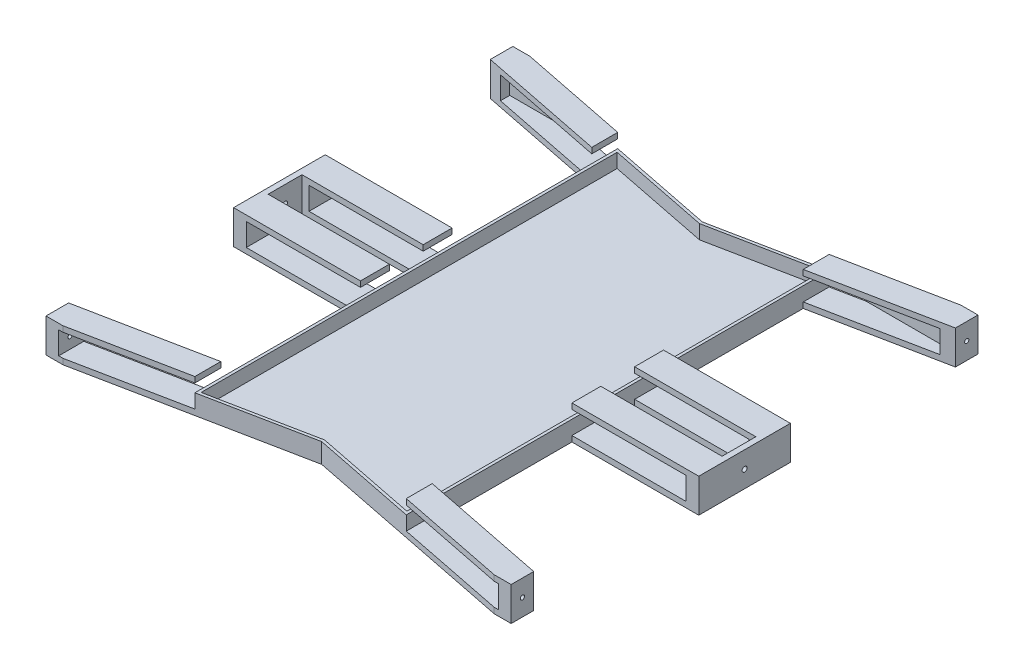
SolidWorks part; units mm, degrees
ref_plane "Front Plane" through (0, 0, 0) normal (0, 0, 1) x (1, 0, 0)
ref_plane "Top Plane" through (0, 0, 0) normal (0, 1, 0) x (1, 0, 0)
ref_plane "Right Plane" through (0, 0, 0) normal (1, 0, 0) x (0, 0, -1)
sketch "Sketch1" plane through (0, 0, 0) normal (0, 1, 0) x (1, 0, 0)
  line L1 (-55, 0) -> (55, 0) construction
  line L2 (165, 32.5) -> (165, -32.5)
  line L3 (165, -32.5) -> (75, -32.5)
  line L4 (75, -32.5) -> (75, -131.6)
  line L5 (75, -131.6) -> (165, -149.6)
  line L6 (165, -149.6) -> (165, -165.6)
  line L7 (165, -165.6) -> (153, -165.6)
  line L8 (153, -165.6) -> (0, -135)
  line L9 (0, -55) -> (0, 55) construction
  line L11 (-165, 32.5) -> (-165, -32.5)
  line L12 (-165, -32.5) -> (-75, -32.5)
  line L13 (-75, -32.5) -> (-75, -131.6)
  line L14 (-75, -131.6) -> (-165, -149.6)
  line L15 (-165, -149.6) -> (-165, -165.6)
  line L16 (-165, -165.6) -> (-153, -165.6)
  line L17 (-153, -165.6) -> (0, -135)
  line L18 (165, 32.5) -> (75, 32.5)
  line L19 (75, 32.5) -> (75, 131.6)
  line L20 (165, 165.6) -> (153, 165.6)
  line L21 (165, 149.6) -> (165, 165.6)
  line L22 (75, 131.6) -> (165, 149.6)
  line L23 (153, 165.6) -> (0, 135)
  line L24 (-165, 149.6) -> (-165, 165.6)
  line L25 (-165, 165.6) -> (-153, 165.6)
  line L26 (-153, 165.6) -> (0, 135)
  line L27 (-75, 131.6) -> (-165, 149.6)
  line L28 (-165, 32.5) -> (-75, 32.5)
  line L29 (-75, 32.5) -> (-75, 131.6)
  line L30 (75, -131.6) -> (75, -150) construction
  line L32 (-75, -131.6) -> (-75, -150) construction
  line L34 (-75, 131.6) -> (-75, 150) construction
  line L36 (75, 131.6) -> (75, 150) construction
  point P21 (165, 0)
  point P33 (-165, 0)
  dimension "D1" = 300
  dimension "D2" = 270
  dimension "D3" = 150
  dimension "D4" = 16
  dimension "D5" = 12
  dimension "D6" = 65
  dimension "D7" = 90
extrude "Boss-Extrude1" add sketch "Sketch1" along normal blind 12 and the other way blind 12
sketch "Sketch2" plane through (0, 0, 165.6) normal (0, 0, 1) x (1, 0, 0)
  line L1 (-156, -8) -> (156, -8)
  line L2 (-156, -8) -> (-156, 8)
  line L3 (-156, 8) -> (156, 8)
  line L4 (156, -8) -> (156, 8)
  line L7 (55, 0) -> (-55, 0) construction
  dimension "D1" = 8
  dimension "D2" = 8
  dimension "D3" = 156
  dimension "D4" = 156
extrude "Cut-Extrude1" cut sketch "Sketch2" against normal blind 320
sketch "Sketch4" plane through (0, 12, 0) normal (0, 1, 0) x (1, 0, 0)
  line L0 (-55, 0) -> (55, 0) construction
  line L1 (-161, 12) -> (-75, 12)
  line L2 (-161, 12) -> (-161, -12)
  line L3 (-161, -12) -> (-75, -12)
  line L4 (-75, 12) -> (-75, -12)
  line L5 (-165, 32.5) -> (-165, -32.5) construction
  line L6 (-75, -32.5) -> (-75, -131.6) construction
  line L7 (0, -55) -> (0, 55) construction
  line L8 (161, -12) -> (75, -12)
  line L9 (75, 12) -> (75, -12)
  line L10 (161, 12) -> (75, 12)
  line L11 (161, 12) -> (161, -12)
  dimension "D1" = 12
  dimension "D2" = 12
  dimension "D3" = 4
extrude "Cut-Extrude2" cut sketch "Sketch4" against normal blind 24
sketch "Sketch6" plane through (0, 0, 0) normal (1, 0, 0) x (0, 0, -1)
  line L0 (-149.6, 0) -> (-165.6, 0) construction
  line L1 (149.6, 0) -> (165.6, 0) construction
  circle A0 centre (-157.6, 0) radius 1.5
  circle A1 centre (157.6, 0) radius 1.5
  point P6 (-157.6, 0)
  point P10 (157.6, 0)
  dimension "D1" = 3
extrude "Cut-Extrude3" cut sketch "Sketch6" against normal through all both and the other way through all
sketch "Sketch7" plane through (165, 0, 0) normal (1, 0, 0) x (0, 0, -1)
  circle A0 centre (0, 0) radius 1.75
  dimension "D1" = 3.5
extrude "Cut-Extrude4" cut sketch "Sketch7" against normal up to surface (330 mm away) up to face at (-165, 0, 0)
sketch "Sketch8" plane through (0, 12, 0) normal (0, 1, 0) x (1, 0, 0)
  line L0 (0, 135) -> (0, -135) construction
  line L1 (156, -12) -> (156, 12) construction
  line L2 (156, 8) -> (144, 8)
  line L3 (156, 8) -> (156, -8)
  line L4 (156, -8) -> (144, -8)
  line L5 (144, 8) -> (144, -8)
  line L6 (-156, 0) -> (165, 0) construction
  line L7 (-156, 12) -> (-156, -12) construction
  line L8 (165, -32.5) -> (165, 32.5) construction
  line L9 (-156, -8) -> (-144, -8)
  line L10 (-144, 8) -> (-144, -8)
  line L11 (-156, 8) -> (-144, 8)
  line L12 (-156, 8) -> (-156, -8)
  point P16 (144, 0)
  dimension "D1" = 16
  dimension "D2" = 12
extrude "Cut-Extrude5" [suppressed] cut sketch "Sketch8" against normal up to surface (5 mm away) up to face at (0, 8, 1.3176)
sketch "Sketch11" plane through (0, 12, 0) normal (0, 1, 0) x (1, 0, 0)
  line L0 (-75, -150) -> (-75, 150)
  line L1 (-153, -165.6) -> (0, -135) construction
  line L2 (0, 135) -> (-153, 165.6) construction
  line L3 (75, 150) -> (75, -150)
  line L4 (153, 165.6) -> (0, 135) construction
  line L5 (0, -135) -> (153, -165.6) construction
  line L6 (75, 32.5) -> (75, 131.6) construction
  line L7 (-75, 131.6) -> (-75, 32.5) construction
  line L8 (0, -135) -> (75, -150)
  line L9 (-75, -150) -> (0, -135)
  line L10 (0, 135) -> (-75, 150)
  line L11 (75, 150) -> (0, 135)
extrude "Cut-Extrude7" cut sketch "Sketch11" against normal up to surface (4 mm away) up to face at (0, 8, 1.3176)
sketch "Sketch12" plane through (0, -8, 0) normal (0, 1, 0) x (1, 0, 0)
  line L0 (-75, 150) -> (-75, -150)
  line L1 (-153, -165.6) -> (0, -135) construction
  line L2 (75, 150) -> (75, -150)
  line L3 (-75, -150) -> (0, -135)
  line L4 (0, -135) -> (75, -150)
  line L5 (-75, 150) -> (0, 135)
  line L6 (0, 135) -> (75, 150)
  line L7 (0, 132.9604) -> (73, 147.5604)
  line L8 (73, 147.5604) -> (73, -147.5604)
  line L9 (0, -132.9604) -> (73, -147.5604)
  line L10 (-73, -147.5604) -> (0, -132.9604)
  line L11 (-73, 147.5604) -> (-73, -147.5604)
  line L12 (-73, 147.5604) -> (0, 132.9604)
  dimension "D1" = 2
extrude "Boss-Extrude2" add sketch "Sketch12" along normal blind 10
equation "\"A\" = 4"
equation "\"D1@Boss-Extrude1\"=3*\"A\""
equation "\"D2@Boss-Extrude1\"=3*\"A\""
equation "\"D1@Sketch2\"=2*\"A\""
equation "\"D2@Sketch2\"=2*\"A\""
equation "\"D1@Sketch4\"=3*\"A\""
equation "\"D2@Sketch4\"=3*\"A\""
equation "\"D3@Sketch4\"=\"A\""
equation "\"D1@Cut-Extrude2\"=6*\"A\""
equation "\"D1@Cut-Extrude1\"=80*\"A\""
equation "\"D3@Sketch2\"=\"A\" * 39"
equation "\"D4@Sketch2\"=\"A\" * 39"
